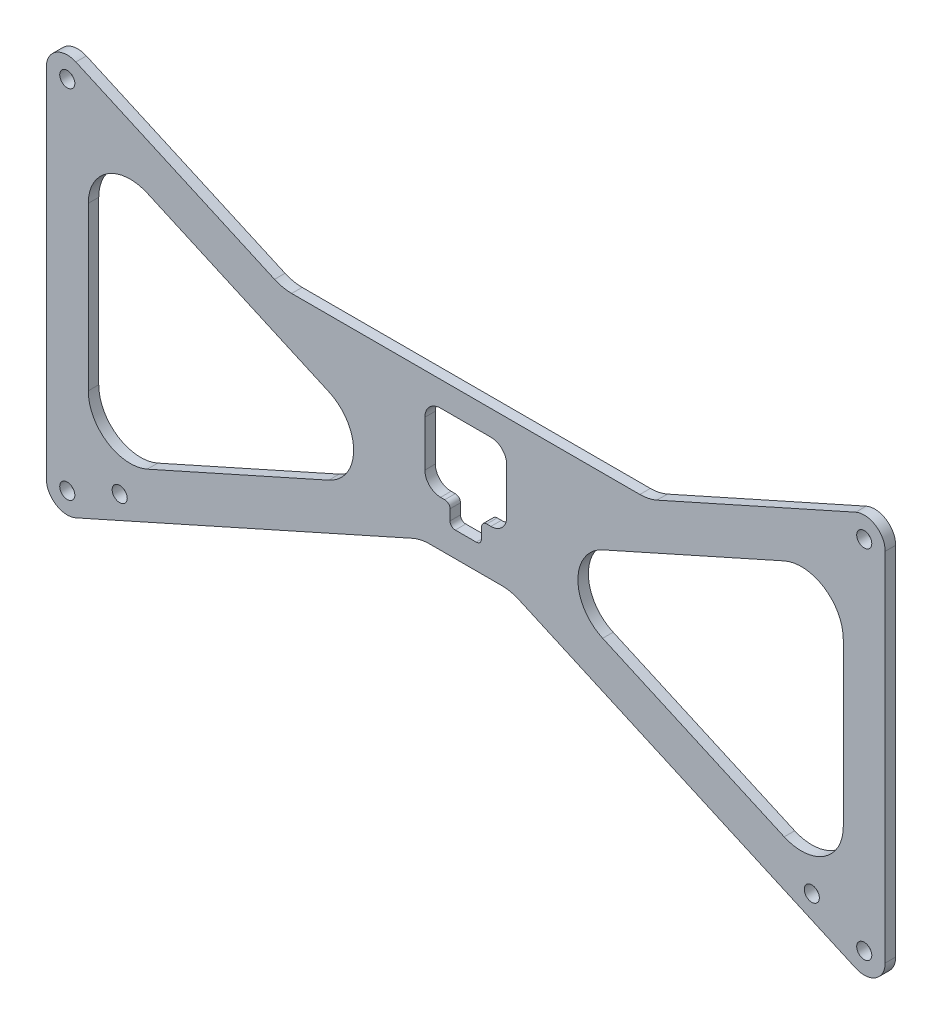
SolidWorks part; units mm, degrees
ref_plane "Front Plane" through (0, 0, 0) normal (0, 0, 1) x (1, 0, 0)
ref_plane "Top Plane" through (0, 0, 0) normal (0, 1, 0) x (1, 0, 0)
ref_plane "Right Plane" through (0, 0, 0) normal (1, 0, 0) x (0, 0, -1)
sketch "Sketch1" plane through (0, 0, 0) normal (0, 0, 1) x (1, 0, 0)
  line L0 (-120.65, -53.975) -> (120.65, 53.975) construction
  line L3 (-114.3, -44.1777) -> (-15.5498, 0)
  line L10 (-118.0569, -59.7714) -> (-13.6323, -13.0552)
  line L11 (-120.65, 53.975) -> (120.65, -53.975) construction
  line L12 (-118.0569, 59.7714) -> (-55.4208, 31.75)
  line L13 (-114.3, 44.1777) -> (-15.5498, 0)
  line L14 (55.4208, 31.75) -> (118.0569, 59.7714)
  line L15 (13.6323, -13.0552) -> (118.0569, -59.7714)
  line L16 (15.5498, 0) -> (114.3, 44.1777)
  line L17 (15.5498, 0) -> (114.3, -44.1777)
  line L18 (-127, 53.975) -> (-127, -53.975)
  line L19 (-114.3, 44.1777) -> (-114.3, -44.1777)
  line L20 (127, 53.975) -> (127, -53.975)
  line L21 (114.3, 44.1777) -> (114.3, -44.1777)
  line L24 (-55.4208, 31.75) -> (55.4208, 31.75)
  line L25 (-13.6323, -13.0552) -> (13.6323, -13.0552)
  arc A4 (-127, -53.975) -> (-118.0569, -59.7714) centre (-120.65, -53.975) ccw
  arc A5 (127, 53.975) -> (118.0569, 59.7714) centre (120.65, 53.975) ccw
  arc A6 (-118.0569, 59.7714) -> (-127, 53.975) centre (-120.65, 53.975) ccw
  arc A7 (118.0569, -59.7714) -> (127, -53.975) centre (120.65, -53.975) ccw
  point P2 (0, 0)
  point P7 (0, 0)
  point P9 (0, 0)
  point P13 (0, 0)
  point P18 (-35.4672, 22.8234)
  point P21 (0, 0)
  point P26 (0, 0)
  dimension "D1" = 254
  dimension "D3" = 6.35
  dimension "D2" = 107.95
  dimension "D4" = 13.0552
  dimension "D6" = 31.75
extrude "Boss-Extrude1" add sketch "Sketch1" along normal blind 3.175
sketch "Sketch2" plane through (0, 0, 3.175) normal (0, 0, 1) x (1, 0, 0)
  line L0 (127, -53.975) -> (127, 53.975) construction
  line L1 (-127, 53.975) -> (-127, -53.975) construction
  line L2 (-107.3681, -41.0766) -> (-102.1819, -52.6694) construction
  line L3 (-114.3, -44.1777) -> (-15.5498, 0) construction
  line L4 (-118.0569, -59.7714) -> (-13.6323, -13.0552) construction
  circle A0 centre (-120.65, 53.975) radius 2.286
  circle A1 centre (-120.65, -53.975) radius 2.286
  circle A2 centre (120.65, -53.975) radius 2.286
  circle A3 centre (120.65, 53.975) radius 2.286
  arc A4 (-118.0569, 59.7714) -> (-127, 53.975) centre (-120.65, 53.975) ccw construction
  arc A5 (-127, -53.975) -> (-118.0569, -59.7714) centre (-120.65, -53.975) ccw construction
  arc A6 (118.0569, -59.7714) -> (127, -53.975) centre (120.65, -53.975) ccw construction
  arc A7 (127, 53.975) -> (118.0569, 59.7714) centre (120.65, 53.975) ccw construction
  circle A8 centre (104.775, -46.873) radius 2.286
  circle A9 centre (-104.775, -46.873) radius 2.286
  point P24 (-104.775, -46.873)
  dimension "D1" = 4.572
  dimension "D2" = 22.225
  dimension "D3" = 22.225
extrude "Cut-Extrude1" cut sketch "Sketch2" against normal through all
fillet "Fillet1" radius 12.7 10 edges at (114.3, -44.1777, 1.5875) (114.3, 44.1777, 1.5875) (15.5498, 0, 1.5875) (-114.3, -44.1777, 1.5875) (-15.5498, 0, 1.5875) (-114.3, 44.1777, 1.5875) (-55.4208, 31.75, 1.5875) (55.4208, 31.75, 1.5875) (13.6323, -13.0552, 1.5875) (-13.6323, -13.0552, 1.5875)
sketch "Sketch3" plane through (0, 0, 3.175) normal (0, 0, 1) x (1, 0, 0)
  line L1 (-12.3825, 24.2094) -> (12.3825, 24.2094)
  line L2 (-12.3825, 24.2094) -> (-12.3825, 0.8334)
  line L4 (12.3825, 24.2094) -> (12.3825, 0.8334)
  line L8 (-12.3825, 0.8334) -> (-4.7625, 0.8334)
  line L9 (-4.7625, 0.8334) -> (-4.7625, -5.5166)
  line L10 (-4.7625, -5.5166) -> (4.7625, -5.5166)
  line L11 (4.7625, -5.5166) -> (4.7625, 0.8334)
  line L12 (4.7625, 0.8334) -> (12.3825, 0.8334)
  line L13 (52.7095, 31.75) -> (-52.7095, 31.75) construction
  line L14 (0, 0) -> (-4.7625, 0) construction
  line L15 (0, 0) -> (4.7625, 0) construction
  dimension "D1" = 6.35
  dimension "D2" = 24.765
  dimension "D3" = 9.525
  dimension "D4" = 7.5406
  dimension "D5" = 23.3759
  dimension "D6" = 5.5166
extrude "Cut-Extrude2" cut sketch "Sketch3" against normal through all
fillet "Fillet2" radius 1.5875 4 edges at (4.7625, -5.5166, 1.5875) (-4.7625, -5.5166, 1.5875) (4.7625, 0.8334, 1.5875) (-4.7625, 0.8334, 1.5875)
fillet "Fillet3" radius 4.7625 4 edges at (12.3825, 0.8334, 1.5875) (12.3825, 24.2094, 1.5875) (-12.3825, 0.8334, 1.5875) (-12.3825, 24.2094, 1.5875)
